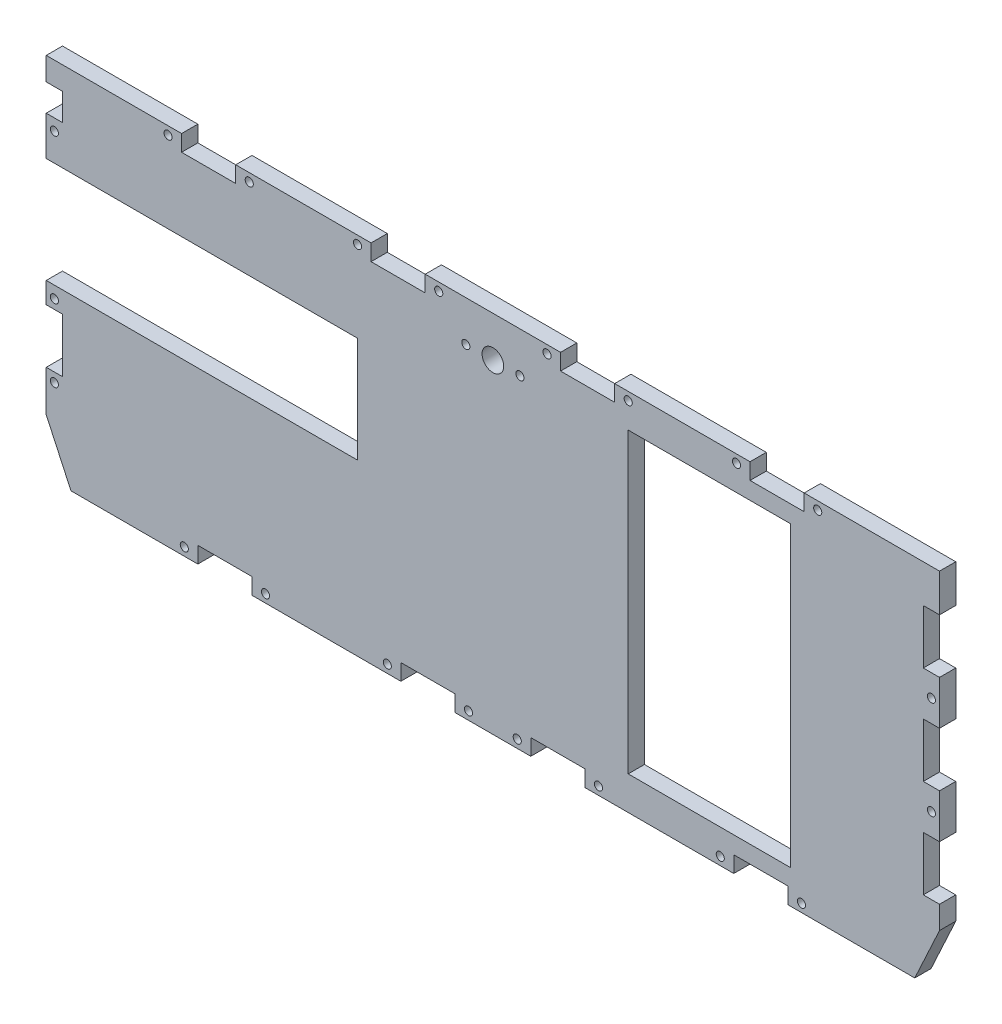
SolidWorks part; units mm, degrees
ref_plane "Plan de face" through (0, 0, 0) normal (0, 0, 1) x (1, 0, 0)
ref_plane "Plan de dessus" through (0, 0, 0) normal (0, 1, 0) x (1, 0, 0)
ref_plane "Plan de droite" through (0, 0, 0) normal (1, 0, 0) x (0, 0, -1)
sketch "Esquisse1" plane through (0, 0, 0) normal (0, 0, 1) x (1, 0, 0)
  line L0 (0, 124.9429) -> (0, -204.46) construction
  line L1 (-165, 96.73) -> (165, 96.73)
  line L2 (165, 96.73) -> (165, -18.27)
  line L3 (165, -18.27) -> (123, -109.0224)
  line L4 (123, -109.0224) -> (-123, -109.0224)
  line L5 (-211.9802, 0) -> (248.5953, 0) construction
  line L6 (-123, -109.0224) -> (-165, -18.27)
  line L7 (-165, -18.27) -> (-165, 96.73)
  dimension "D2" = 165
  dimension "D3" = 330
  dimension "D4" = 100
  dimension "D5" = 115
  dimension "D6" = 100
  dimension "D7" = 246
  dimension "D8" = 205.7524
  dimension "D9" = 96.73
  dimension "D10" = 115
extrude "Boss.-Extru.1" add sketch "Esquisse1" along normal blind 6
sketch "Esquisse3" plane through (0, 0, 0) normal (0, 0, -1) x (-1, 0, 0)
  line L0 (165, 96.73) -> (165, -18.27) construction
  line L1 (165, -3.06) -> (159, -3.06)
  line L2 (165, -3.06) -> (165, 16.94)
  line L3 (165, 16.94) -> (159, 16.94)
  line L4 (159, -3.06) -> (159, 16.94)
  line L5 (123, -109.0224) -> (-123, -109.0224) construction
  line L6 (165, 78.2326) -> (159, 78.2326)
  line L7 (165, 78.2326) -> (165, 88.2326)
  line L8 (165, 88.2326) -> (159, 88.2326)
  line L9 (159, 78.2326) -> (159, 88.2326)
  line L10 (-14, -38.02) -> (-14, -32.02)
  line L11 (109, -38.02) -> (89, -38.02)
  line L12 (109, -38.02) -> (109, -32.02)
  line L13 (109, -32.02) -> (89, -32.02)
  line L15 (0, -209.4812) -> (0, 177.1799) construction
  line L16 (-110, 84.355) -> (-50, 84.355)
  line L17 (-165, 82.73) -> (-159, 82.73)
  line L18 (89, -38.02) -> (89, -32.02)
  line L19 (34, -38.02) -> (14, -38.02)
  line L20 (34, -38.02) -> (34, -32.02)
  line L21 (34, -32.02) -> (14, -32.02)
  line L22 (-165, 82.73) -> (-165, 62.73)
  line L23 (-165, 62.73) -> (-159, 62.73)
  line L24 (-159, 82.73) -> (-159, 62.73)
  line L25 (-165, 46.44) -> (-159, 46.44)
  line L26 (-165, 46.44) -> (-165, 26.44)
  line L27 (-165, 26.44) -> (-159, 26.44)
  line L28 (-159, 46.44) -> (-159, 26.44)
  line L29 (-165, 10.15) -> (-159, 10.15)
  line L30 (-165, 96.73) -> (165, 96.73) construction
  line L31 (115, 96.73) -> (95, 96.73)
  line L32 (115, 96.73) -> (115, 90.73)
  line L33 (115, 90.73) -> (95, 90.73)
  line L34 (95, 96.73) -> (95, 90.73)
  line L35 (-25, 96.73) -> (-25, 90.73)
  line L36 (45, 96.73) -> (25, 96.73)
  line L37 (45, 96.73) -> (45, 90.73)
  line L38 (45, 90.73) -> (25, 90.73)
  line L39 (25, 96.73) -> (25, 90.73)
  line L40 (-45, 90.73) -> (-25, 90.73)
  line L41 (-45, 96.73) -> (-45, 90.73)
  line L42 (-45, 96.73) -> (-25, 96.73)
  line L43 (-95, 96.73) -> (-95, 90.73)
  line L44 (-115, 90.73) -> (-95, 90.73)
  line L45 (-115, 96.73) -> (-115, 90.73)
  line L46 (-115, 96.73) -> (-95, 96.73)
  line L47 (-165, 10.15) -> (-165, -9.85)
  line L48 (14, -38.02) -> (14, -32.02)
  line L49 (-34, -32.02) -> (-14, -32.02)
  line L50 (-34, -38.02) -> (-34, -32.02)
  line L51 (-34, -38.02) -> (-14, -38.02)
  line L52 (-165, -9.85) -> (-159, -9.85)
  line L53 (165, 63.73) -> (50, 63.73)
  line L54 (165, 63.73) -> (165, 24.73)
  line L55 (165, 24.73) -> (50, 24.73)
  line L56 (-159, 10.15) -> (-159, -9.85)
  line L57 (-89, -38.02) -> (-89, -32.02)
  line L58 (-109, -32.02) -> (-89, -32.02)
  line L59 (-109, -38.02) -> (-109, -32.02)
  line L60 (-109, -38.02) -> (-89, -38.02)
  line L62 (-110, 84.355) -> (-110, -25.645)
  line L63 (-110, -25.645) -> (-50, -25.645)
  line L64 (-50, 84.355) -> (-50, -25.645)
  line L65 (-165, -18.27) -> (-165, 96.73) construction
  line L66 (50, 63.73) -> (50, 24.73)
  dimension "D1" = 20
  dimension "D2" = 6
  dimension "D3" = 6
  dimension "D4" = 10
  dimension "D5" = 6
  dimension "D6" = 20
  dimension "D7" = 60
  dimension "D8" = 55
  dimension "D9" = 8.4974
  dimension "D10" = 20
  dimension "D11" = 20
  dimension "D12" = 50
  dimension "D13" = 50
  dimension "D14" = 6
  dimension "D15" = 110
  dimension "D16" = 56
  dimension "D17" = 55
  dimension "D18" = 20
  dimension "D19" = 20
  dimension "D20" = 20
  dimension "D21" = 6
  dimension "D22" = 6
  dimension "D23" = 20
  dimension "D24" = 71.0024
  dimension "D25" = 71.0024
  dimension "D26" = 33
  dimension "D27" = 39
  dimension "D28" = 115
  dimension "D29" = 6.375
  dimension "D30" = 15.21
  dimension "D31" = 6
  dimension "D32" = 6
  dimension "D33" = 6
  dimension "D34" = 14
  dimension "D35" = 16.29
  dimension "D36" = 16.29
extrude "Enlèv. mat.-Extru.2" cut sketch "Esquisse3" against normal blind 6
sketch "Esquisse4" plane through (0, 0, 0) normal (0, 0, -1) x (-1, 0, 0)
  line L0 (159, 78.2326) -> (165, 78.2326) construction
  line L1 (115, 90.73) -> (115, 96.73) construction
  line L2 (120.102, -35.02) -> (4.7601, -35.02) construction
  line L3 (14, -32.02) -> (14, -38.02) construction
  line L4 (34, -38.02) -> (34, -32.02) construction
  line L5 (89, -32.02) -> (89, -38.02) construction
  line L6 (26.5287, 81.73) -> (-31.7243, 81.73) construction
  line L7 (109, -38.02) -> (109, -32.02) construction
  line L8 (165, 78.2326) -> (165, 63.73) construction
  line L9 (-120.102, -35.02) -> (-4.7601, -35.02) construction
  line L10 (-25, 96.73) -> (25, 96.73) construction
  line L11 (143.8632, 93.73) -> (-5, 93.73) construction
  line L12 (45, 96.73) -> (95, 96.73) construction
  line L13 (-162, -27.3544) -> (-162, 100.425) construction
  line L14 (95, 96.73) -> (95, 90.73) construction
  line L15 (45, 90.73) -> (45, 96.73) construction
  line L16 (25, 96.73) -> (25, 90.73) construction
  line L17 (0, 142.2997) -> (0, -202.2086) construction
  line L18 (-165, -18.27) -> (-165, -9.85) construction
  line L19 (-80, 84.355) -> (-80, -25.645) construction
  line L21 (165, 16.94) -> (159, 16.94) construction
  line L22 (162, -8.8216) -> (162, 103.5789) construction
  line L25 (-50, 84.355) -> (-110, 84.355) construction
  line L26 (-110, -25.645) -> (-50, -25.645) construction
  line L27 (-159, 46.44) -> (-165, 46.44) construction
  line L28 (-165, 26.44) -> (-159, 26.44) construction
  line L31 (159, -3.06) -> (165, -3.06) construction
  circle A0 centre (162, 20.335) radius 1.5
  circle A1 centre (114, -35.02) radius 1.5
  circle A2 centre (162, 73.9826) radius 1.5
  circle A3 centre (84, -35.02) radius 1.5
  circle A4 centre (39, -35.02) radius 1.5
  circle A5 centre (162, -6.46) radius 1.5
  circle A6 centre (9, -35.02) radius 1.5
  circle A7 centre (-9, -35.02) radius 1.5
  circle A8 centre (-39, -35.02) radius 1.5
  circle A9 centre (-84, -35.02) radius 1.5
  circle A10 centre (120, 93.73) radius 1.5
  circle A11 centre (-114, -35.02) radius 1.5
  circle A12 centre (90, 93.73) radius 1.5
  circle A13 centre (0, 81.73) radius 4
  circle A14 centre (50, 93.73) radius 1.5
  circle A15 centre (20, 93.73) radius 1.5
  circle A16 centre (-162, 18.29) radius 1.5
  circle A17 centre (-162, 54.585) radius 1.5
  circle A18 centre (-20, 93.73) radius 1.5
  circle A19 centre (-50, 93.73) radius 1.5
  circle A20 centre (-90, 93.73) radius 1.5
  circle A21 centre (-120, 93.73) radius 1.5
  circle A22 centre (-10, 81.73) radius 1.5
  circle A23 centre (10, 81.73) radius 1.5
  dimension "D3" = 3
  dimension "D10" = 3
  dimension "D11" = 3
  dimension "D12" = 3
  dimension "D13" = 5
  dimension "D14" = 5
  dimension "D18" = 3
  dimension "D19" = 3
  dimension "D29" = 3
  dimension "D30" = 8.15
  dimension "D31" = 3
  dimension "D32" = 10
  dimension "D33" = 3
  dimension "D34" = 3
  dimension "D35" = 10
  dimension "D40" = 5
  dimension "D5" = 3.395
  dimension "D8" = 5
  dimension "D15" = 5
  dimension "D16" = 5
  dimension "D20" = 3.4
  dimension "D17" = 3
  dimension "D21" = 3
  dimension "D22" = 3
  dimension "D23" = 3
  dimension "D25" = 8
  dimension "D27" = 8.145
  dimension "D9" = 3
  dimension "D7" = 3
  dimension "D24" = 3
  dimension "D6" = 4.25
  dimension "D26" = 3
  dimension "D28" = 3
  dimension "D36" = 15
  dimension "D38" = 5
  dimension "D42" = 5
extrude "Enlèv. mat.-Extru.3" cut sketch "Esquisse4" against normal blind 6
sketch "Esquisse5" plane through (0, 0, 0) normal (0, 0, -1) x (-1, 0, 0)
  line L0 (45, 96.73) -> (95, 96.73) construction
  line L1 (209.7155, -38.02) -> (-246.3297, -38.02)
  line L2 (209.7155, -38.02) -> (209.7155, -174.249)
  line L3 (209.7155, -174.249) -> (-246.3297, -174.249)
  line L4 (-246.3297, -38.02) -> (-246.3297, -174.249)
  dimension "D1" = 134.75
extrude "Enlèv. mat.-Extru.4" cut sketch "Esquisse5" against normal blind 6
